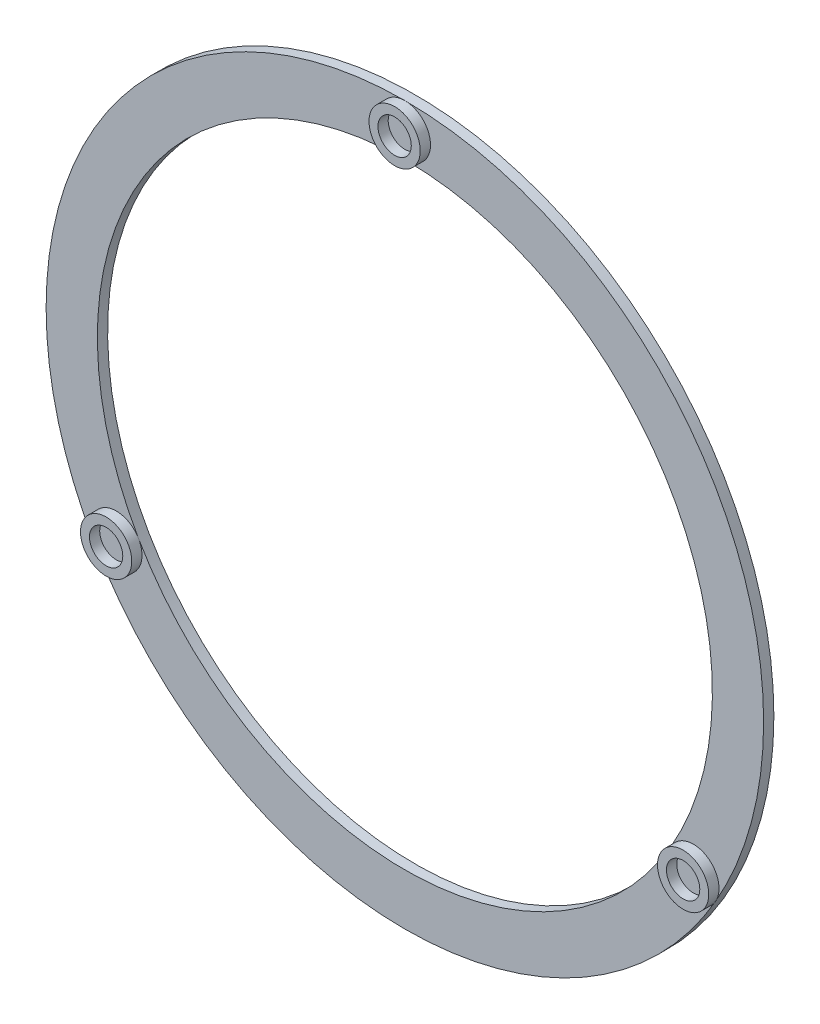
SolidWorks part; units mm, degrees
ref_plane "Front Plane" through (0, 0, 0) normal (0, 0, 1) x (1, 0, 0)
ref_plane "Top Plane" through (0, 0, 0) normal (0, 1, 0) x (1, 0, 0)
ref_plane "Right Plane" through (0, 0, 0) normal (1, 0, 0) x (0, 0, -1)
sketch "Sketch1" plane through (0, 0, 0) normal (0, 0, 1) x (1, 0, 0)
  circle A0 centre (0, 0) radius 300
  circle A1 centre (0, 0) radius 350
extrude "Boss-Extrude1" add sketch "Sketch1" along normal blind 10
sketch "Sketch2" plane through (0, 0, 10) normal (0, 0, 1) x (1, 0, 0)
  line L1 (0, 350) -> (0, 300) construction
  circle A0 centre (0, 0) radius 300 construction
  circle A1 centre (0, 325) radius 16.25
  circle A4 centre (0, 325) radius 25
  circle A5 centre (281.4583, -162.5) radius 25
  circle A6 centre (-281.4583, -162.5) radius 25
  circle A9 centre (281.4583, -162.5) radius 16.25
  circle A10 centre (-281.4583, -162.5) radius 16.25
  point P17 (0, 0)
  point P18 (0, 0)
  point P20 (0, 0)
  dimension "D3" = 50
  dimension "D4" = 3
  dimension "D5" = 32.5
  dimension "D1" = 325
  dimension "D2" = 3
extrude "Boss-Extrude2" add sketch "Sketch2" along normal blind 10
